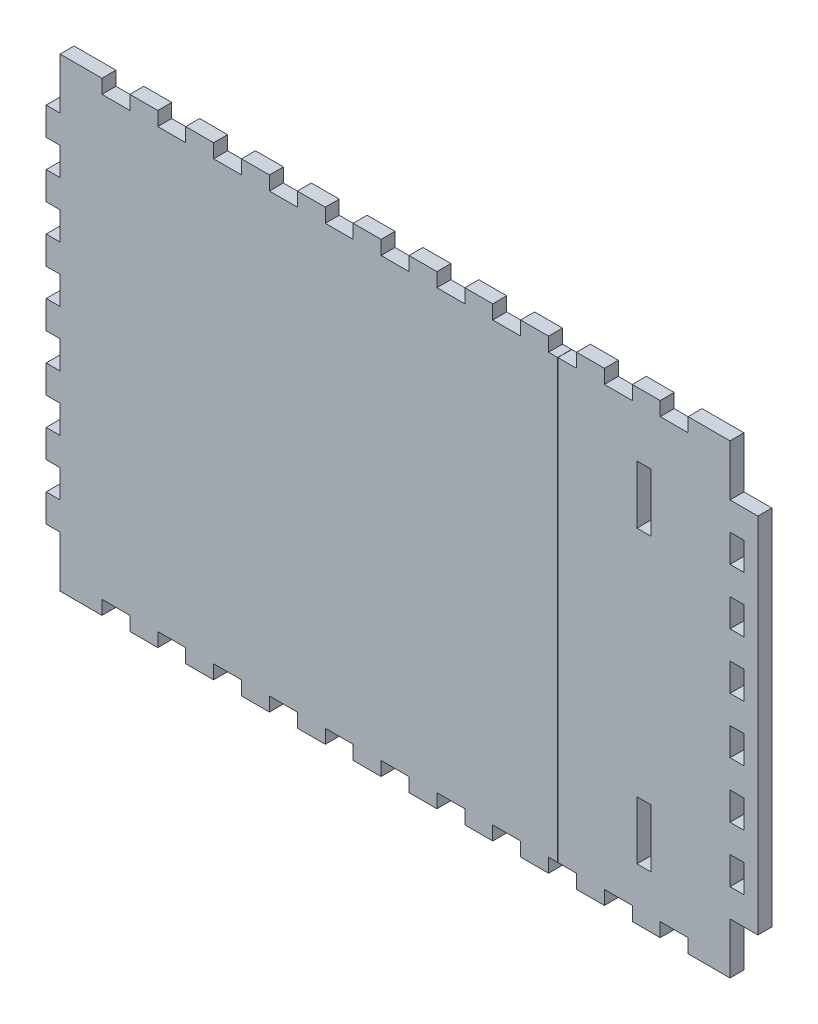
SolidWorks part; units mm, degrees
ref_plane "Front Plane" through (0, 0, 0) normal (0, 0, 1) x (1, 0, 0)
ref_plane "Top Plane" through (0, 0, 0) normal (0, 1, 0) x (1, 0, 0)
ref_plane "Right Plane" through (0, 0, 0) normal (1, 0, 0) x (0, 0, -1)
sketch "Model" plane through (0, 0, 0) normal (0, 0, 1) x (1, 0, 0)
  line L0 (209, 203) -> (209, 181)
  line L1 (209, 181) -> (203, 181)
  line L2 (203, 181) -> (203, 169)
  line L3 (203, 169) -> (209, 169)
  line L4 (209, 169) -> (209, 157)
  line L5 (209, 157) -> (203, 157)
  line L6 (203, 157) -> (203, 145)
  line L7 (203, 145) -> (209, 145)
  line L8 (209, 145) -> (209, 133)
  line L9 (209, 133) -> (203, 133)
  line L10 (203, 133) -> (203, 121)
  line L11 (203, 121) -> (209, 121)
  line L12 (209, 121) -> (209, 109)
  line L13 (209, 109) -> (203, 109)
  line L14 (203, 109) -> (203, 97)
  line L15 (203, 97) -> (209, 97)
  line L16 (209, 97) -> (209, 85)
  line L17 (209, 85) -> (203, 85)
  line L18 (203, 85) -> (203, 73)
  line L19 (203, 73) -> (209, 73)
  line L20 (209, 73) -> (209, 61)
  line L21 (209, 61) -> (203, 61)
  line L22 (203, 61) -> (203, 49)
  line L23 (203, 49) -> (209, 49)
  line L24 (209, 49) -> (209, 37)
  line L25 (209, 37) -> (203, 37)
  line L26 (203, 37) -> (203, 25)
  line L27 (203, 25) -> (209, 25)
  line L28 (209, 25) -> (209, 13)
  line L29 (209, 13) -> (209, 3)
  line L30 (209, 3) -> (227, 3)
  line L31 (227, 3) -> (227, 9)
  line L32 (227, 9) -> (239, 9)
  line L33 (239, 9) -> (239, 3)
  line L34 (239, 3) -> (251, 3)
  line L35 (251, 3) -> (251, 9)
  line L36 (251, 9) -> (263, 9)
  line L37 (263, 9) -> (263, 3)
  line L38 (263, 3) -> (275, 3)
  line L39 (275, 3) -> (275, 9)
  line L40 (275, 9) -> (287, 9)
  line L41 (287, 9) -> (287, 3)
  line L42 (287, 3) -> (299, 3)
  line L43 (299, 3) -> (299, 9)
  line L44 (299, 9) -> (311, 9)
  line L45 (311, 9) -> (311, 3)
  line L46 (311, 3) -> (323, 3)
  line L47 (323, 3) -> (323, 9)
  line L48 (323, 9) -> (335, 9)
  line L49 (335, 9) -> (335, 3)
  line L50 (335, 3) -> (347, 3)
  line L51 (347, 3) -> (347, 9)
  line L52 (347, 9) -> (359, 9)
  line L53 (359, 9) -> (359, 3)
  line L54 (359, 3) -> (371, 3)
  line L55 (371, 3) -> (371, 9)
  line L56 (371, 9) -> (383, 9)
  line L57 (383, 9) -> (383, 3)
  line L58 (383, 3) -> (395, 3)
  line L59 (395, 3) -> (395, 9)
  line L60 (395, 9) -> (407, 9)
  line L61 (407, 9) -> (407, 3)
  line L62 (407, 3) -> (419, 3)
  line L63 (419, 3) -> (419, 9)
  line L64 (419, 9) -> (431, 9)
  line L65 (431, 9) -> (431, 3)
  line L66 (431, 3) -> (443, 3)
  line L67 (443, 3) -> (443, 9)
  line L68 (443, 9) -> (455, 9)
  line L69 (455, 9) -> (455, 3)
  line L70 (455, 3) -> (467, 3)
  line L71 (467, 3) -> (467, 9)
  line L72 (467, 9) -> (479, 9)
  line L73 (479, 9) -> (479, 3)
  line L74 (479, 3) -> (491, 3)
  line L75 (491, 3) -> (497, 3)
  line L76 (497, 3) -> (497, 25)
  line L77 (497, 25) -> (503, 25)
  line L78 (503, 25) -> (503, 37)
  line L79 (503, 37) -> (497, 37)
  line L80 (497, 37) -> (497, 49)
  line L81 (497, 49) -> (503, 49)
  line L82 (503, 49) -> (503, 61)
  line L83 (503, 61) -> (497, 61)
  line L84 (497, 61) -> (497, 73)
  line L85 (497, 73) -> (503, 73)
  line L86 (503, 73) -> (503, 85)
  line L87 (503, 85) -> (497, 85)
  line L88 (497, 85) -> (497, 97)
  line L89 (497, 97) -> (503, 97)
  line L90 (503, 97) -> (503, 109)
  line L91 (503, 109) -> (497, 109)
  line L92 (497, 109) -> (497, 121)
  line L93 (497, 121) -> (503, 121)
  line L94 (503, 121) -> (503, 133)
  line L95 (503, 133) -> (497, 133)
  line L96 (497, 133) -> (497, 145)
  line L97 (497, 145) -> (503, 145)
  line L98 (503, 145) -> (503, 157)
  line L99 (503, 157) -> (497, 157)
  line L100 (497, 157) -> (497, 169)
  line L101 (497, 169) -> (503, 169)
  line L102 (503, 169) -> (503, 181)
  line L103 (503, 181) -> (497, 181)
  line L104 (497, 181) -> (497, 193)
  line L105 (497, 193) -> (497, 203)
  line L106 (497, 203) -> (479, 203)
  line L107 (479, 203) -> (479, 197)
  line L108 (479, 197) -> (467, 197)
  line L109 (467, 197) -> (467, 203)
  line L110 (467, 203) -> (455, 203)
  line L111 (455, 203) -> (455, 197)
  line L112 (455, 197) -> (443, 197)
  line L113 (443, 197) -> (443, 203)
  line L114 (443, 203) -> (431, 203)
  line L115 (431, 203) -> (431, 197)
  line L116 (431, 197) -> (419, 197)
  line L117 (419, 197) -> (419, 203)
  line L118 (419, 203) -> (407, 203)
  line L119 (407, 203) -> (407, 197)
  line L120 (407, 197) -> (395, 197)
  line L121 (395, 197) -> (395, 203)
  line L122 (395, 203) -> (383, 203)
  line L123 (383, 203) -> (383, 197)
  line L124 (383, 197) -> (371, 197)
  line L125 (371, 197) -> (371, 203)
  line L126 (371, 203) -> (359, 203)
  line L127 (359, 203) -> (359, 197)
  line L128 (359, 197) -> (347, 197)
  line L129 (347, 197) -> (347, 203)
  line L130 (347, 203) -> (335, 203)
  line L131 (335, 203) -> (335, 197)
  line L132 (335, 197) -> (323, 197)
  line L133 (323, 197) -> (323, 203)
  line L134 (323, 203) -> (311, 203)
  line L135 (311, 203) -> (311, 197)
  line L136 (311, 197) -> (299, 197)
  line L137 (299, 197) -> (299, 203)
  line L138 (299, 203) -> (287, 203)
  line L139 (287, 203) -> (287, 197)
  line L140 (287, 197) -> (275, 197)
  line L141 (275, 197) -> (275, 203)
  line L142 (275, 203) -> (263, 203)
  line L143 (263, 203) -> (263, 197)
  line L144 (263, 197) -> (251, 197)
  line L145 (251, 197) -> (251, 203)
  line L146 (251, 203) -> (239, 203)
  line L147 (239, 203) -> (239, 197)
  line L148 (239, 197) -> (227, 197)
  line L149 (227, 197) -> (227, 203)
  line L150 (227, 203) -> (215, 203)
  line L151 (215, 203) -> (209, 203)
extrude "Boss-Extrude1" add sketch "Model" along normal blind 6
sketch "Sketch2" plane through (0, 0, 6) normal (0, 0, 1) x (1, 0, 0)
  line L0 (497, 181) -> (497, 203) construction
  line L1 (422.9, 218.155) -> (423, 218.155)
  line L2 (422.9, 218.155) -> (422.9, -17.155)
  line L3 (422.9, -17.155) -> (423, -17.155)
  line L4 (423, 218.155) -> (423, -17.155)
  line L5 (423, 100.5) -> (503, 100.5)
  line L6 (503, 97) -> (503, 109) construction
  line L7 (457, 163) -> (423, 163)
  line L9 (463, 163) -> (497, 163)
  line L11 (497, 157) -> (497, 169) construction
  line L12 (457, 175.5) -> (463, 175.5)
  line L13 (457, 175.5) -> (457, 150.5)
  line L14 (457, 150.5) -> (463, 150.5)
  line L15 (463, 175.5) -> (463, 150.5)
  line L16 (457, 50.5) -> (463, 50.5)
  line L19 (463, 25.5) -> (463, 50.5)
  line L20 (457, 25.5) -> (463, 25.5)
  line L21 (457, 25.5) -> (457, 50.5)
  dimension "D1" = 0.1
  dimension "D2" = 74
  dimension "D3" = 6
  dimension "D4" = 25
  dimension "D5" = 50
extrude "Cut-Extrude1" cut sketch "Sketch2" against normal blind 6 contours L21 L20 L19 L16 | L4 L1 L2 L3 | L13 L14 L15 L12 region at (422.95, 100.5, 6) region at (460, 38, 6)
sketch "Sketch4" plane through (503, 0, 0) normal (1, 0, 0) x (0, 0, -1)
  line L1 (-6, 181) -> (0, 181)
  line L2 (-6, 181) -> (-6, 25)
  line L3 (-6, 25) -> (0, 25)
  line L4 (0, 181) -> (0, 25)
extrude "Boss-Extrude2" add sketch "Sketch4" along normal blind 6
sketch "Sketch3" plane through (0, 0, 6) normal (0, 0, 1) x (1, 0, 0)
